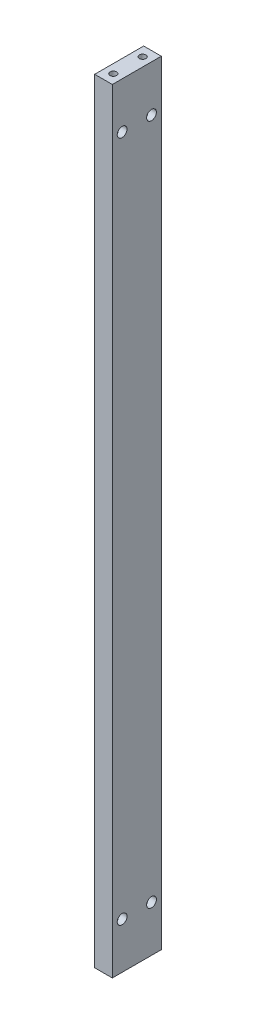
SolidWorks part; units mm, degrees
material "Beech"
ref_plane "Front Plane" through (0, 0, 0) normal (0, 0, 1) x (1, 0, 0)
ref_plane "Top Plane" through (0, 0, 0) normal (0, 1, 0) x (1, 0, 0)
ref_plane "Right Plane" through (0, 0, 0) normal (1, 0, 0) x (0, 0, -1)
sketch "Sketch1" plane through (0, 0, 0) normal (0, 1, 0) x (1, 0, 0)
  line L1 (0, 0) -> (18, 0)
  line L2 (0, 0) -> (0, 50)
  line L3 (0, 50) -> (18, 50)
  line L4 (18, 0) -> (18, 50)
  dimension "D1" = 18
  dimension "D2" = 50
extrude "base" add sketch "Sketch1" along normal blind 789.8
hole_wizard "end bolt holes for inserts" positions "Sketch2" profile "Sketch3" hole size "M6" standard "ANSI Metric"
sketch "Sketch2" plane through (0, 0, 0) normal (0, -1, 0) x (-1, 0, 0)
  line L1 (-9, 50) -> (-9, 0)
  line L2 (-18, 50) -> (0, 50) construction
  line L3 (0, 0) -> (-18, 0) construction
  line L4 (-9, 10) -> (-18, 25)
  line L5 (-18, 0) -> (-18, 50) construction
  line L6 (-18, 25) -> (-9, 40)
  point P10 (-9, 40)
  point P12 (-9, 10)
  dimension "D1" = 30
sketch "Sketch3" plane through (9, 0, -40) normal (1, 0, 0) x (0, 0, -1)
  line L0 (0, 0) -> (0, 58.9828)
  line L1 (0, 58.9828) -> (3.3, 57)
  line L2 (3.3, 57) -> (3.3, 0)
  line L5 (3.3, 0) -> (0, 0)
  line L10 (0, 58.9828) -> (-3.3, 57) construction
  line L11 (0, -6.35) -> (0, 107.95) construction
  dimension "Hole Dia." = 6.6
  dimension "Hole Depth" = 57
  dimension "Drill Angle" = 118
ref_axis "bottom bolt hole axis" through (9, 57, -10) along (0, -1, 0)
ref_axis "top bolt hole axis" through (9, 57, -40) along (0, -1, 0)
hole_wizard "cross dowel bolt clearance holes" positions "Sketch4" profile "Sketch5" hole size "Ø10.0" standard "ANSI Metric" end condition through all
sketch "Sketch4" plane through (0, 0, 0) normal (-1, 0, 0) x (0, 0, 1)
  line L0 (-40, 57) -> (-40, 0) construction
  line L1 (-10, 57) -> (-10, 0) construction
  line L2 (-13.3, 57) -> (-6.7, 57) construction
  line L3 (-13.3, 57) -> (-6.7, 57)
  point P0 (-40, 47)
  point P4 (-10, 47)
  point P11 (0, 0)
  point P12 (-40, 47)
  point P13 (-40, 47)
  point P14 (-40, 47)
  dimension "D1" = 10
sketch "Sketch5" plane through (0, 47, -40) normal (0, 1, 0) x (0, 0, 1)
  line L0 (0, 0) -> (0, 18)
  line L1 (0, 18) -> (5, 18)
  line L2 (5, 18) -> (5, 0)
  line L5 (5, 0) -> (0, 0)
  line L11 (0, -6.35) -> (0, 107.95) construction
  dimension "Thru Hole Dia." = 10
  dimension "Thru Hole Depth" = 18
ref_plane "midplane along length" through (0, 394.9, 0) normal (0, -1, 0) x (-1, 0, 0)
mirror "mirror end bolt holes" about plane through (0, 394.9, 0) normal (0, -1, 0) of "cross dowel bolt clearance holes", "end bolt holes for inserts"
equation "\"board_thickness\" = 18mm"
equation "\"way_width\"= 75mm"
equation "\"way_thickness\"= 50mm"
equation "\"radial_clearance\"= 0.1mm"
equation "\"slider_width\"= \"way_width\"-2* \"radial_clearance\" - 2*0.65"
equation "\"slider_thickness\" = \"way_thickness\" - 2 * \"radial_clearance\""
equation "\"column_width\"= \"way_width\" + 2 * \"board_thickness\""
equation "\"boxway_slot_width\" = 50mm"
equation "\"keeper_rail_width\" = (\"column_width\" - \"boxway_slot_width\")/2"
equation "\"slider_length\" = 125mm"
equation "\"nut_diameter\"= 22mm"
equation "\"nut_length\"= 15mm"
equation "\"leadscrew_diameter\"= 10mm"
equation "\"leadscrew_radial_clearance\"= 1mm"
equation "\"bearing_bolt_pattern_width\" = 30mm"
equation "\"bearing_bolt_pattern_height\" = 75mm"
equation "\"desktop_bolt_pattern_width\" = 30mm"
equation "\"desktop_bolt_pattern_height\" = 30mm"
equation "\"bearing_bolt_nut_counterbore_diameter\" = 12mm"
equation "\"bearing_bolt_nut_counterbore_depth\"= 10mm"
equation "\"desktop_depth\"= 500mm"
equation "\"desktop_width\"= 650mm"
equation "\"desktop_thickness\"= 18mm"
equation "\"leg_height\"=100mm"
equation "\"leg_width\"=18mm"
equation "\"leg_length\"=500mm"
equation "\"lap_joint_height\" = 50mm"
equation "\"lap_dowel_diameter\"= 8mm"
equation "\"lap_dowel_hole_z_spacing\"=30"
equation "\"D1@Sketch1\"=\"board_thickness\""
equation "\"D2@Sketch1\"=\"lap_joint_height\""
equation "\"D1@Sketch2\"=\"lap_dowel_hole_z_spacing\""
